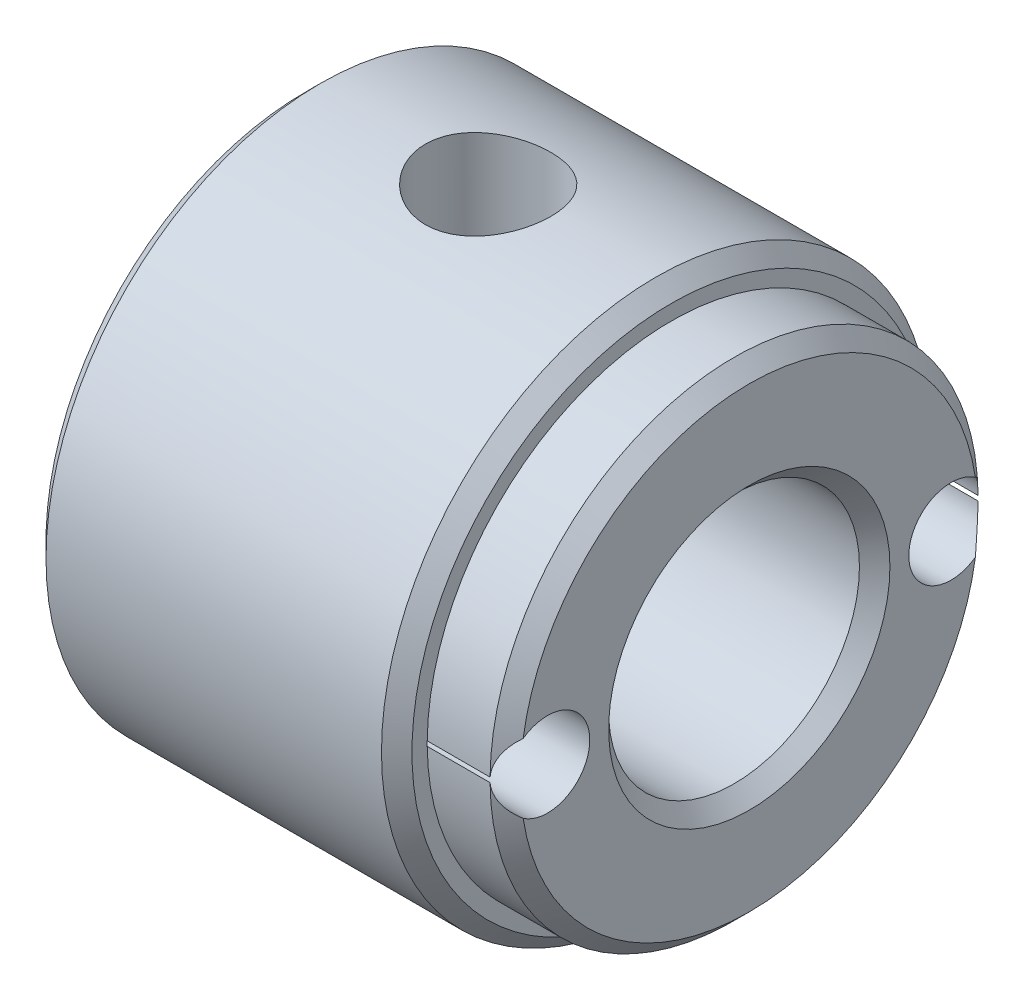
SolidWorks part; units mm, degrees
ref_plane "Front Plane" through (0, 0, 0) normal (0, 0, 1) x (1, 0, 0)
ref_plane "Top Plane" through (0, 0, 0) normal (0, 1, 0) x (1, 0, 0)
ref_plane "Right Plane" through (0, 0, 0) normal (1, 0, 0) x (0, 0, -1)
sketch "Sketch1" plane through (0, 0, 0) normal (1, 0, 0) x (0, 0, -1)
  line L0 (0, 0) -> (0, 0.7417) construction
  line L1 (-3.2639, 0) -> (-6.35, 0) construction
  circle A0 centre (0, 0) radius 6.35
  circle A1 centre (0, 0) radius 6.35
  circle A2 centre (0, 0) radius 3.2639
  circle A3 centre (-5.2515, 0) radius 1.1
  circle A5 centre (0, 0) radius 7.1438
  circle A6 centre (5.2515, 0) radius 1.1
  dimension "D1" = 12.7
  dimension "D2" = 6.5278
  dimension "D3" = 2.2
  dimension "D4" = 14.2875
  dimension "D5" = 10.5029
extrude "Inner Side Extrude" add sketch "Sketch1" along normal blind 2.032 contours A0 A2 A3 A6 region at (0, 0, -3.9718)
extrude "Outer Side Extrude" add sketch "Sketch1<3>" against normal blind 9.525 contours A0 A2 A3 A6 | A5 A0 region at (0, 0, -3.9718) region at (0, 0, 6.9417)
sketch "Sketch1<3>" plane through (0, 0, 0) normal (1, 0, 0) x (0, 0, -1) same geometry as "Sketch1"
sketch "Sketch2" plane through (0, 0, 0) normal (0, 1, 0) x (1, 0, 0)
  line L0 (-9.525, 7.1438) -> (-9.525, -7.1438) construction
  line L1 (-9.525, 0) -> (0, 0) construction
  circle A0 centre (-4.7625, 0) radius 1.632
  point P0 (-9.525, 0)
  dimension "D1" = 3.2639
extrude "Clevis Pin Cut" cut sketch "Sketch2" against normal through all and the other way through all
chamfer "Chamfer so Steve Doesn't cut himself" distance 0.3969 angle 45 6 edges at (-9.525, 0, -3.2639) (2.032, 0, -3.2639) (-9.525, 0, -7.1438) (0, 0, -7.1438) (2.032, 6.35, 0) (2.032, -6.35, 0)
